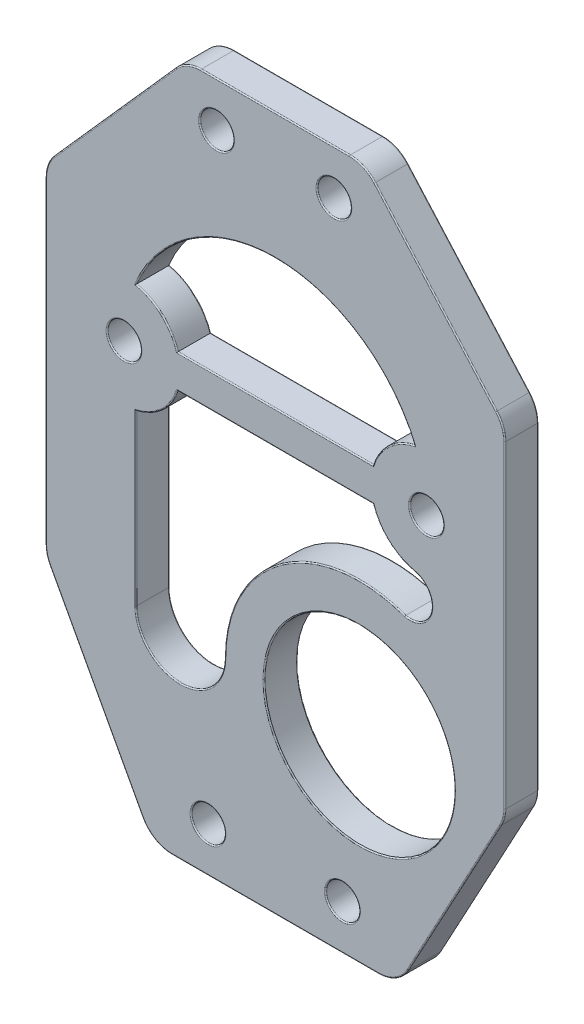
SolidWorks part; units mm, degrees
ref_plane "Front Plane" through (0, 0, 0) normal (0, 0, 1) x (1, 0, 0)
ref_plane "Top Plane" through (0, 0, 0) normal (0, 1, 0) x (1, 0, 0)
ref_plane "Right Plane" through (0, 0, 0) normal (1, 0, 0) x (0, 0, -1)
sketch "Sketch1" plane through (0, 0, 0) normal (0, 0, 1) x (1, 0, 0)
  line L0 (0, 0) -> (0, 62) construction
  line L6 (11, 0) -> (-11, 0)
  line L7 (-11, 0) -> (-20.5, 17.5997)
  line L8 (-20.5, 17.5997) -> (-20.5, 47.8997)
  line L9 (-20.5, 47.8997) -> (-7.9898, 62)
  line L10 (-7.9898, 62) -> (7.9898, 62)
  line L11 (11, 0) -> (20.5, 17.5997)
  line L12 (20.5, 17.5997) -> (20.5, 47.8997)
  line L13 (20.5, 47.8997) -> (7.9898, 62)
  line L14 (7.5, 17.5997) -> (20.5, 17.5997) construction
  line L15 (-13.5, 37.5997) -> (13.5, 37.5997) construction
  line L16 (-8.7303, 39.0997) -> (8.7303, 39.0997)
  line L17 (-8.7303, 39.0997) -> (8.7303, 39.0997) construction
  line L18 (-8.7303, 39.0997) -> (-8.7303, 36.0997) construction
  line L19 (-8.7303, 36.0997) -> (8.7303, 36.0997) construction
  line L20 (8.7303, 39.0997) -> (8.7303, 36.0997) construction
  line L21 (-8.7303, 39.0997) -> (8.7303, 36.0997) construction
  line L22 (-8.7303, 36.0997) -> (8.7303, 39.0997) construction
  line L23 (-8.7303, 36.0997) -> (8.7303, 36.0997)
  line L24 (13.5, 37.5997) -> (11.5932, 28.88) construction
  line L25 (-12.4318, 32.7151) -> (-12.4318, 17.5997)
  circle A3 centre (-5.2398, 58) radius 1.5
  circle A4 centre (-13.5, 37.5997) radius 1.5
  circle A5 centre (-6, 4) radius 1.5
  circle A6 centre (6, 4) radius 1.5
  circle A7 centre (13.5, 37.5997) radius 1.5
  circle A8 centre (5.2398, 58) radius 1.5
  circle A9 centre (7.5, 17.5997) radius 8.5
  circle A10 centre (-13.5, 37.5997) radius 5 construction
  circle A11 centre (13.5, 37.5997) radius 5 construction
  circle A12 centre (7.5, 17.5997) radius 12 construction
  arc A13 (-12.4318, 42.4843) -> (12.4318, 42.4843) centre (0, 37.2213) cw
  arc A14 (-12.4318, 42.4843) -> (-8.7303, 39.0997) centre (-13.5, 37.5997) cw
  arc A15 (-8.7303, 36.0997) -> (-12.4318, 32.7151) centre (-13.5, 37.5997) cw
  arc A16 (8.7303, 39.0997) -> (12.4318, 42.4843) centre (13.5, 37.5997) cw
  arc A17 (8.7303, 36.0997) -> (12.4318, 32.7151) centre (13.5, 37.5997) ccw
  arc A18 (12.4318, 32.7151) -> (11.5932, 28.88) centre (12.0125, 30.7976) cw
  arc A19 (11.5932, 28.88) -> (-4.5, 17.5997) centre (7.5, 17.5997) ccw
  arc A20 (-12.4318, 17.5997) -> (-4.5, 17.5997) centre (-8.4659, 17.5997) ccw
  point P34 (0, 37.5997)
  point P40 (0, 50.7213)
  point P51 (0, 0)
  dimension "D9" = 30.3
  dimension "D4" = 3
  dimension "D5" = 3
  dimension "D6" = 3
  dimension "D16" = 17
  dimension "D21" = 13.5
  dimension "D1" = 62
  dimension "D2" = 6
  dimension "D3" = 4
  dimension "D7" = 11
  dimension "D8" = 20
  dimension "D10" = 10.3
  dimension "D11" = 7
  dimension "D12" = 2.75
  dimension "D13" = 4
  dimension "D14" = 18.85
  dimension "D15" = 20.5
  dimension "D17" = 13
  dimension "D22" = 3
  dimension "D23" = 12.4318
  dimension "D18" = 3.5
  dimension "D19" = 3.5
  dimension "D20" = 3.5
extrude "Boss-Extrude1" add sketch "Sketch1" along normal blind 3
fillet "Fillet1" radius 3 8 edges at (-7.9898, 62, 1.5) (-20.5, 47.8997, 1.5) (-20.5, 17.5997, 1.5) (-11, 0, 1.5) (11, 0, 1.5) (20.5, 17.5997, 1.5) (20.5, 47.8997, 1.5) (7.9898, 62, 1.5)
fillet "Fillet2" radius 0.1 68 edges at (0.6123, 27.4262, 0) (-8.4659, 13.6338, 0) (-12.4318, 25.1574, 0) (-10.126, 33.9097, 0) (0, 36.0997, 0) (10.126, 33.9097, 0) (13.9301, 30.3783, 0) (10.126, 41.2897, 0) (0, 39.0997, 0) (-10.126, 41.2897, 0) (0, 50.7213, 0) (16, 17.5997, 0) (12, 37.5997, 0) (-4.5, 4, 0) (-3.7398, 58, 0) (-20.3047, 47.8256, 0) (-20.5, 32.5592, 0) (-20.4086, 17.6228, 0) (-15.9951, 9.2539, 0) (-10.7472, 0.4237, 0) (0, 0, 0) (10.7472, 0.4237, 0) (15.9951, 9.2539, 0) (20.4086, 17.6228, 0) (20.5, 32.5592, 0) (20.3047, 47.8256, 0) (14.3146, 54.8714, 0) (7.8712, 61.7361, 0) (0, 62, 0) (-7.8712, 61.7361, 0) (-14.3146, 54.8714, 0) (-12, 37.5997, 0) (4.5, 4, 0) (3.7398, 58, 0) (0, 36.0997, 3) (-10.126, 33.9097, 3) (-12.4318, 25.1574, 3) (-8.4659, 13.6338, 3) (0.6123, 27.4262, 3) (13.9301, 30.3783, 3) (10.126, 33.9097, 3) (16, 17.5997, 3) (3.7398, 58, 3) (12, 37.5997, 3) (4.5, 4, 3) (-4.5, 4, 3) (-12, 37.5997, 3) (-3.7398, 58, 3) (7.8712, 61.7361, 3) (14.3146, 54.8714, 3) (20.3047, 47.8256, 3) (20.5, 32.5592, 3) (20.4086, 17.6228, 3) (15.9951, 9.2539, 3) (10.7472, 0.4237, 3) (0, 0, 3) (-10.7472, 0.4237, 3) (-15.9951, 9.2539, 3) (-20.4086, 17.6228, 3) (-20.5, 32.5592, 3) (-20.3047, 47.8256, 3) (-14.3146, 54.8714, 3) (-7.8712, 61.7361, 3) (0, 62, 3) (0, 39.0997, 3) (10.126, 41.2897, 3) (0, 50.7213, 3) (-10.126, 41.2897, 3)
